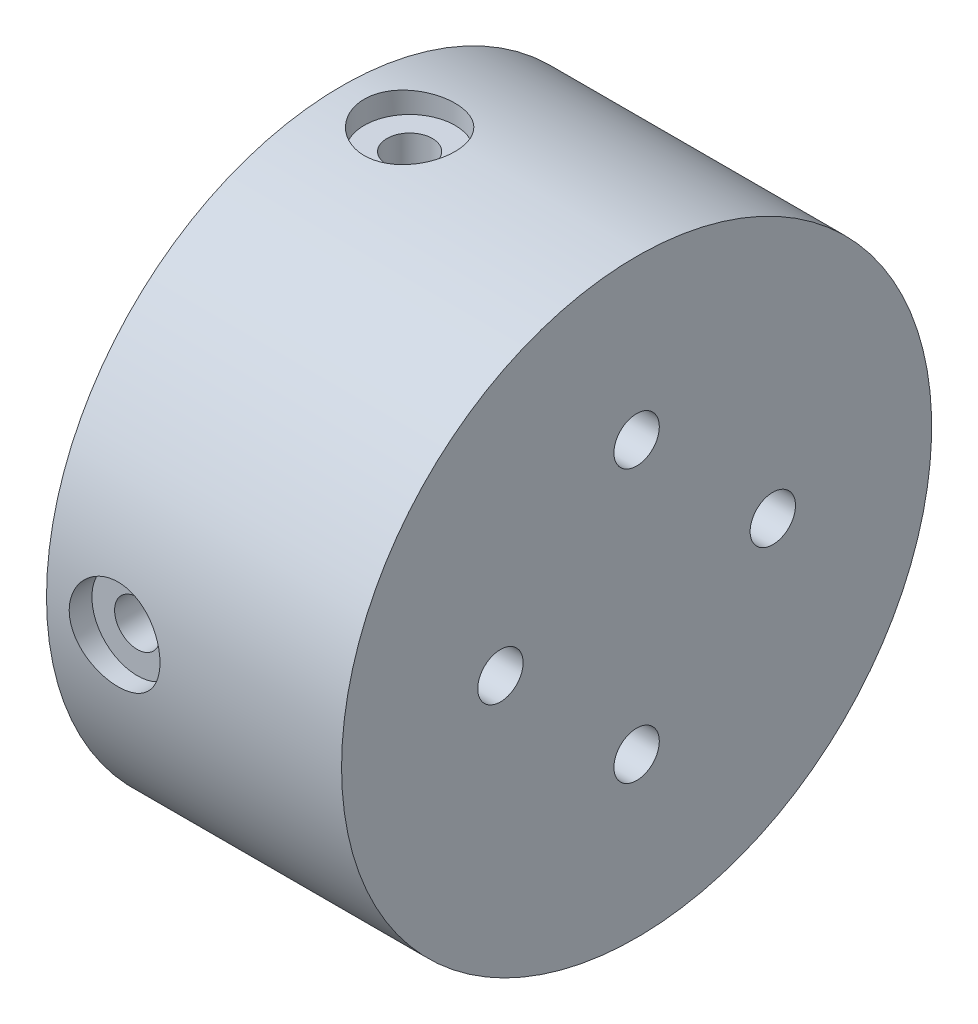
SolidWorks part; units mm, degrees
ref_plane "Спереди" through (0, 0, 0) normal (0, 0, 1) x (1, 0, 0)
ref_plane "Сверху" through (0, 0, 0) normal (0, 1, 0) x (1, 0, 0)
ref_plane "Справа" through (0, 0, 0) normal (1, 0, 0) x (0, 0, -1)
sketch "Эскиз1" plane through (0, 0, 0) normal (0, 0, 1) x (1, 0, 0)
  line L0 (0, 0) -> (67.9269, 0) construction
  line L1 (0, 13) -> (13, 13)
  line L2 (13, 13) -> (13, 0)
  line L6 (10, 0) -> (10, 10)
  line L7 (10, 10) -> (0, 10)
  line L8 (0, 10) -> (0, 13)
  line L9 (10, 0) -> (13, 0)
  dimension "D1" = 20
  dimension "D2" = 3
  dimension "D3" = 10
  dimension "D4" = 13
  dimension "D5" = 3
revolve "Повернуть1" add sketch "Эскиз1" angle 360 about L0
sketch "Эскиз2" plane through (13, 0, 0) normal (1, 0, 0) x (0, 0, -1)
  circle A0 centre (0, 6) radius 1
  dimension "D1" = 2
  dimension "D2" = 6
  dimension "D3" = 6
extrude "Вырез-Вытянуть1" cut sketch "Эскиз2" against normal up to next contours A0
ref_axis "Ось1" through (10, 0, 0) along (-1, 0, 0)
pattern_circular "Круговой массив1" count 4 over 360 about axis through (10, 0, 0) along (-1, 0, 0) of "Вырез-Вытянуть1"
ref_plane "Плоскость1" through (0, 0, 13) normal (0, 0, 1) x (1, 0, 0)
sketch "Эскиз5" plane through (0, 0, 13) normal (0, 0, 1) x (1, 0, 0)
  line L0 (0, 13) -> (0, -13) construction
  circle A0 centre (3, 0) radius 1
  dimension "D1" = 2
  dimension "D2" = 3
  dimension "D3" = 3
extrude "Вырез-Вытянуть2" cut sketch "Эскиз5" against normal blind 10 contours A0
pattern_circular "Круговой массив3" count 4 over 360 about axis through (10, 0, 0) along (-1, 0, 0) of "Вырез-Вытянуть2"
sketch "Эскиз7" plane through (0, 0, 13) normal (0, 0, 1) x (1, 0, 0)
  circle A0 centre (3, 0) radius 2
  dimension "D1" = 4
extrude "Вырез-Вытянуть3" cut sketch "Эскиз7" against normal blind 1 contours A0
pattern_circular "Круговой массив4" count 4 over 360 about axis through (10, 0, 0) along (-1, 0, 0) of "Вырез-Вытянуть3"
